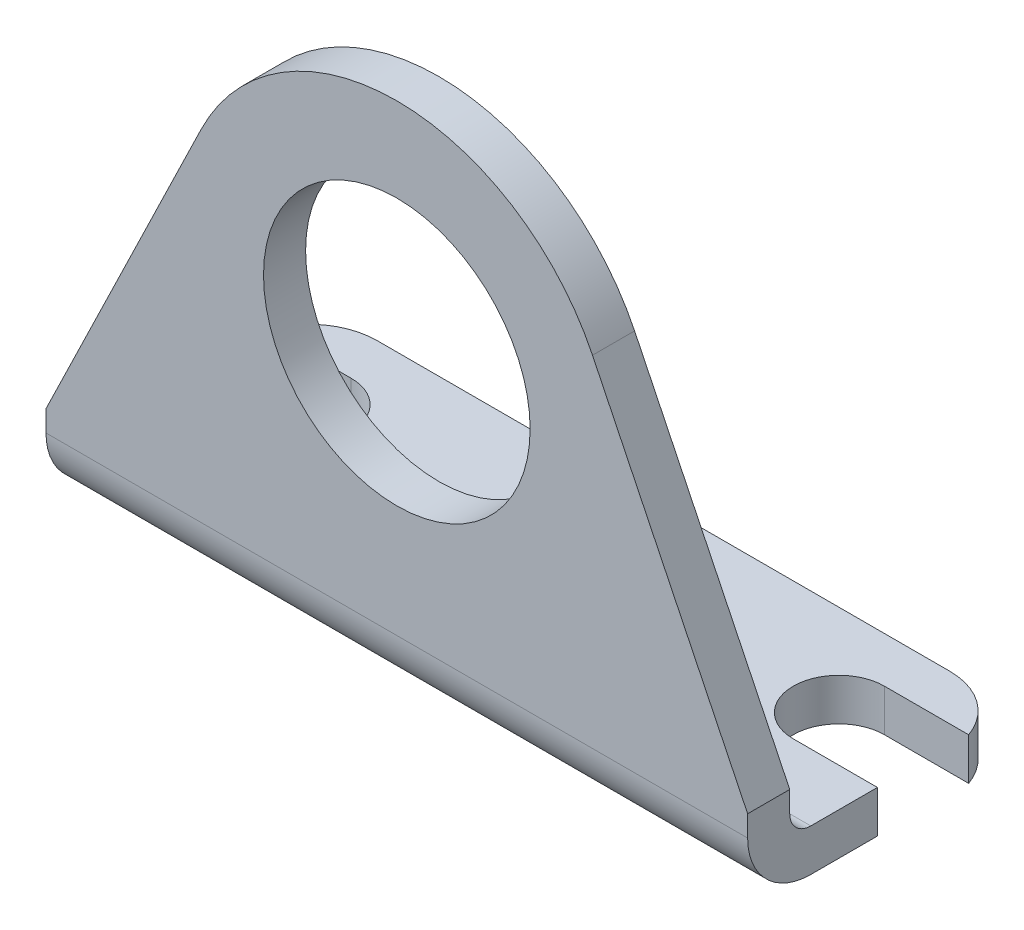
SolidWorks part; units mm, degrees
material "AISI 304"
ref_plane "Front Plane" through (0, 0, 0) normal (0, 0, 1) x (1, 0, 0)
ref_plane "Top Plane" through (0, 0, 0) normal (0, 1, 0) x (1, 0, 0)
ref_plane "Right Plane" through (0, 0, 0) normal (1, 0, 0) x (0, 0, -1)
sketch "Sketch1" plane through (0, 0, 0) normal (0, 1, 0) x (1, 0, 0)
  line L0 (-12.7, 0) -> (12.7, 0) construction
  line L1 (0, 3.302) -> (0, -6.35) construction
  line L2 (-9.652, 1.651) -> (-12.7, 1.651)
  line L3 (-12.7, 1.651) -> (-12.7, -1.651)
  line L4 (-9.652, -1.651) -> (-12.7, -1.651)
  line L5 (9.652, 1.651) -> (12.7, 1.651)
  line L6 (12.7, 1.651) -> (12.7, -1.651)
  line L7 (9.652, -1.651) -> (12.7, -1.651)
  arc A0 (-9.652, -1.651) -> (-9.652, 1.651) centre (-9.652, 0) ccw
  arc A1 (9.652, 1.651) -> (9.652, -1.651) centre (9.652, 0) ccw
  dimension "Width" = 25.4
  dimension "Depth" = 9.652
  dimension "Hole Dia" = 3.302
  dimension "Hole Location" = 9.652
  dimension "D5" = 9.652
  dimension "HL" = 6.35
sketch "Sketch2" plane through (0, 0, 0) normal (0, 0, 1) x (1, 0, 0)
  line L0 (-12.7, 0) -> (12.7, 0)
  line L1 (12.7, 0) -> (12.7, 3.048)
  line L2 (12.7, 3.048) -> (7.0831, 14.6154)
  line L3 (-12.7, 0) -> (-12.7, 3.048)
  line L4 (-12.7, 3.048) -> (-7.0831, 14.6154)
  line L5 (0, 0) -> (0, 11.176) construction
  line L6 (-12.7, 1.524) -> (12.7, 1.524) construction
  arc A0 (-7.0831, 14.6154) -> (7.0831, 14.6154) centre (0, 11.176) cw
  circle A1 centre (0, 11.176) radius 4.826
  dimension "Thickness" = 1.524
  dimension "ID" = 9.652
  dimension "Radius" = 7.874
  dimension "C to C" = 11.176
  dimension "Height" = 19.05
  dimension "D5" = 3.048
sketch "Sketch3" plane through (0, 0, 0) normal (0, 0, 1) x (1, 0, 0)
  line L5 (-12.7, 0) -> (12.7, 0)
  line L6 (12.7, 0) -> (12.7, 3.048)
  line L7 (12.7, 3.048) -> (7.0831, 14.6154)
  line L8 (-7.0831, 14.6154) -> (-12.7, 3.048)
  line L9 (-12.7, 3.048) -> (-12.7, 0)
  line L10 (-12.7, 0) -> (12.7, 0)
  line L11 (12.7, 0) -> (12.7, 3.048)
  line L12 (12.7, 3.048) -> (7.0831, 14.6154)
  line L13 (-7.0831, 14.6154) -> (-12.7, 3.048)
  line L14 (-12.7, 3.048) -> (-12.7, 0)
  circle A1 centre (0, 11.176) radius 4.826
  circle A2 centre (0, 11.176) radius 4.826
  arc A3 (7.0831, 14.6154) -> (-7.0831, 14.6154) centre (0, 11.176) ccw
  arc A4 (7.0831, 14.6154) -> (-7.0831, 14.6154) centre (0, 11.176) ccw
  dimension "D1" = 0
  dimension "D2" = 0
extrude "Boss-Extrude1" add sketch "Sketch3" along normal up to vertex (6.35 mm away) and the other way up to vertex (3.302 mm away) up to point (0, 0, 6.35) other way up to point (0, 0, -3.302)
sketch "Sketch4" plane through (0, 0, 0) normal (0, 1, 0) x (1, 0, 0)
  line L0 (-12.7, 1.651) -> (-12.7, -1.651) construction
  line L1 (-9.652, -1.651) -> (-12.7, -1.651) construction
  line L2 (-9.652, 1.651) -> (-12.7, 1.651) construction
  line L3 (9.652, 1.651) -> (12.7, 1.651) construction
  line L4 (9.652, -1.651) -> (12.7, -1.651) construction
  line L6 (-12.7, 1.651) -> (-12.7, -1.651)
  line L7 (-9.652, -1.651) -> (-12.7, -1.651)
  line L8 (-9.652, 1.651) -> (-12.7, 1.651)
  line L9 (9.652, 1.651) -> (12.7, 1.651)
  line L10 (9.652, -1.651) -> (12.7, -1.651)
  line L12 (12.7, -1.651) -> (12.7, 1.651)
  arc A0 (-9.652, -1.651) -> (-9.652, 1.651) centre (-9.652, 0) ccw construction
  arc A1 (9.652, 1.651) -> (9.652, -1.651) centre (9.652, 0) ccw construction
  arc A2 (-9.652, -1.651) -> (-9.652, 1.651) centre (-9.652, 0) ccw
  arc A3 (9.652, 1.651) -> (9.652, -1.651) centre (9.652, 0) ccw
extrude "Cut-Extrude1" cut sketch "Sketch4" along normal through all
sketch "Sketch5" plane through (-12.7, 0, 0) normal (-1, 0, 0) x (0, 0, 1)
  line L0 (6.35, 14.6154) -> (6.35, 3.048) construction
  line L1 (-3.302, 19.05) -> (4.826, 19.05)
  line L2 (-3.302, 19.05) -> (-3.302, 1.524)
  line L3 (-3.302, 1.524) -> (4.064, 1.524)
  line L4 (4.826, 19.05) -> (4.826, 2.286)
  line L5 (-3.302, 3.048) -> (-3.302, 0) construction
  line L6 (6.35, 19.05) -> (-3.302, 19.05) construction
  line L7 (-3.302, 0) -> (6.35, 0) construction
  line L8 (6.35, 3.048) -> (6.35, 0) construction
  line L9 (4.064, 0) -> (6.35, 0)
  line L10 (6.35, 2.286) -> (6.35, 0)
  arc A0 (4.064, 1.524) -> (4.826, 2.286) centre (4.064, 2.286) ccw
  arc A1 (4.064, 0) -> (6.35, 2.286) centre (4.064, 2.286) ccw
  dimension "D3" = 0.762
  dimension "D4" = 2.286
  dimension "D1" = 1.524
  dimension "Thickness" = 1.524
extrude "Cut-Extrude2" cut sketch "Sketch5" against normal through all
fillet "Fillet1" radius 2.4765 2 edges at (-12.7, 0.762, -3.302) (12.7, 0.762, -3.302)
equation "\"D4@Sketch5\" = \"D1@Sketch5\"+\"D3@Sketch5\""
equation "\"D5@Sketch1\" = \"Hole Location@Sketch1\""
equation "\"D3@Sketch5\" = \"Thickness@Sketch5\"/2"
equation "\"D1@Fillet1\" = \"Hole Dia@Sketch1\"*.750"
equation "\"Thickness@Sketch5\" = \"Thickness@Sketch2\""
equation "\"D1@Sketch5\" = \"Thickness@Sketch5\""
